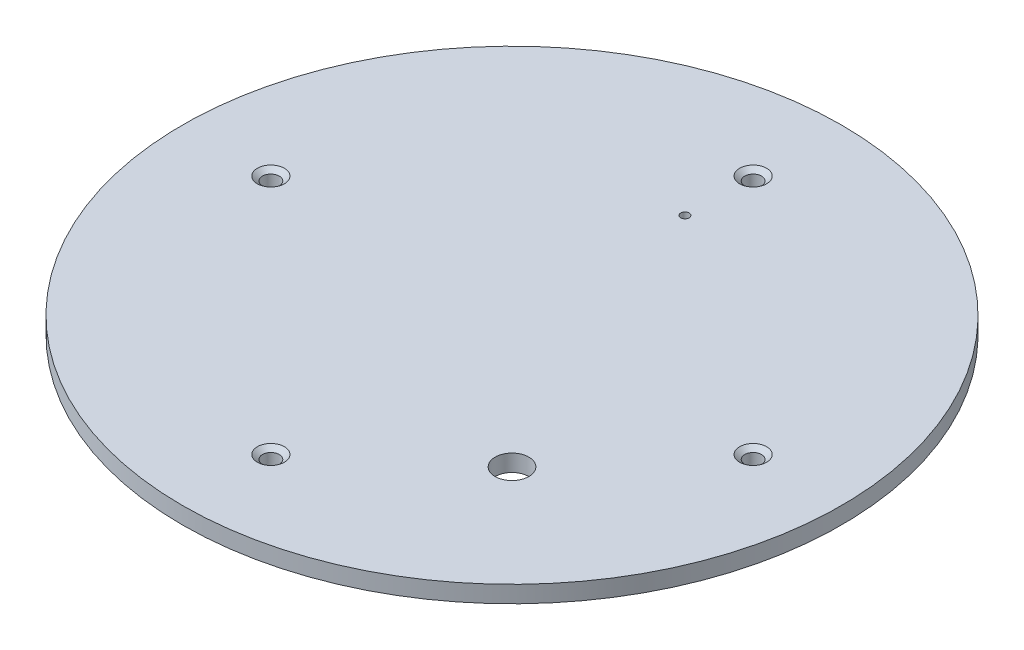
SolidWorks part; units mm, degrees
material "1060 Alloy"
ref_plane "Front Plane" through (0, 0, 0) normal (0, 0, 1) x (1, 0, 0)
ref_plane "Top Plane" through (0, 0, 0) normal (0, 1, 0) x (1, 0, 0)
ref_plane "Right Plane" through (0, 0, 0) normal (1, 0, 0) x (0, 0, -1)
sketch "Sketch1" plane through (0, 0, 0) normal (0, 1, 0) x (1, 0, 0)
  circle A0 centre (0, 0) radius 19.53
  dimension "D1" = 39.06
extrude "Boss-Extrude1" add sketch "Sketch1" along normal blind 1
hole_wizard "CSK for M2 Flat Head Machine Screw1" positions "Sketch2" profile "Sketch3" countersink size "M2" standard "ANSI Metric" end condition through all
sketch "Sketch2" plane through (0, 1, 0) normal (0, 1, 0) x (1, 0, 0)
  point P0 (0, 14.29)
  point P2 (14.29, 0)
  point P4 (0, -14.29)
  point P6 (-14.29, 0)
  dimension "D1" = 14.29
  dimension "D2" = 14.29
  dimension "D3" = 14.29
  dimension "D4" = 14.29
sketch "Sketch3" plane through (0, 1, -14.29) normal (1, 0, 0) x (0, 0, 1)
  line L0 (0, 0) -> (0, 1)
  line L1 (0, 1) -> (0.5, 1)
  line L2 (0.5, 1) -> (0.5, 0.2517)
  line L3 (0.5, 0.2517) -> (0.8, 0)
  line L5 (0.8, 0) -> (0, 0)
  line L6 (-0.5, 0.2517) -> (-0.8, 0) construction
  line L11 (0, -6.35) -> (0, 107.95) construction
  dimension "Thru Hole Dia." = 1
  dimension "Thru Hole Depth" = 1
  dimension "Near C'Sink Dia." = 1.6
  dimension "Near C'Sink Angle" = 100
sketch "Sketch4" plane through (0, 1, 0) normal (0, 1, 0) x (1, 0, 0)
  circle A0 centre (0, 10.25) radius 0.25
  dimension "D1" = 0.5
  dimension "D2" = 10.25
extrude "Cut-Extrude1" cut sketch "Sketch4" against normal through all both and the other way through all
sketch "Sketch5" plane through (0, 0, 0) normal (0, -1, 0) x (1, 0, 0)
  line L0 (0, 0) -> (12.768, 12.768) construction
  line L1 (0, 0) -> (24.3444, 0) construction
  circle A0 centre (7.7782, 7.7782) radius 1
  dimension "D2" = 2
  dimension "D1" = 11
  dimension "D3" = 45
extrude "Cut-Extrude2" cut sketch "Sketch5" against normal through all both and the other way through all
